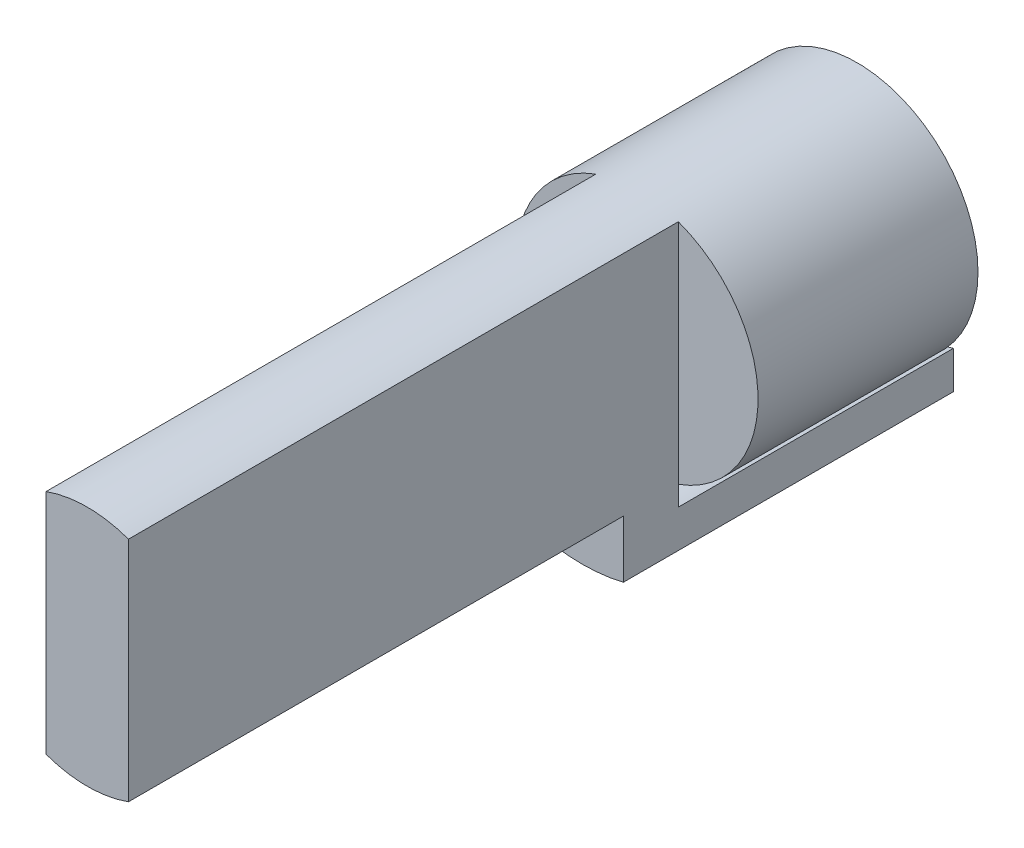
SolidWorks part; units mm, degrees
ref_plane "Front Plane" through (0, 0, 0) normal (0, 0, 1) x (1, 0, 0)
ref_plane "Top Plane" through (0, 0, 0) normal (0, 1, 0) x (1, 0, 0)
ref_plane "Right Plane" through (0, 0, 0) normal (1, 0, 0) x (0, 0, -1)
sketch "Sketch2" plane through (0, 0, 0) normal (0, 0, 1) x (1, 0, 0)
  circle A0 centre (0, 0) radius 11
  dimension "D1" = 22
extrude "Boss-Extrude1" add sketch "Sketch2" along normal blind 20
sketch "Sketch3" plane through (0, 0, 20) normal (0, 0, 1) x (1, 0, 0)
  line L2 (3.75, 10.3411) -> (3.75, -10.3411)
  line L4 (-3.75, 10.3411) -> (-3.75, -10.3411)
  line L5 (3.3225, 10.4862) -> (-3.3225, -10.4862) construction
  line L6 (3.3225, -10.4862) -> (-3.3225, 10.4862) construction
  circle A0 centre (0, 0) radius 11 construction
  arc A1 (-3.75, -10.3411) -> (3.75, -10.3411) centre (0, 0) ccw
  arc A2 (3.75, 10.3411) -> (-3.75, 10.3411) centre (0, 0) ccw
  point P0 (0, 0)
extrude "Boss-Extrude2" add sketch "Sketch3" along normal blind 50
sketch "Sketch4" plane through (0, 0, 70) normal (0, 0, 1) x (1, 0, 0)
  line L0 (-3.75, -10.3411) -> (-3.75, -12.1599)
  line L1 (3.75, -10.3411) -> (3.75, -12.1599)
  arc A0 (-3.75, -12.1599) -> (3.75, -12.1599) centre (0, 0) ccw
  arc A2 (-3.75, -10.3411) -> (3.75, -10.3411) centre (0, 0) ccw
  dimension "D1" = 25.45
extrude "Boss-Extrude3" add sketch "Sketch4" along normal blind 5 from surface starting at face at (-7.375, 0, 20)
sketch "Sketch5" plane through (0, 0, 70) normal (0, 0, 1) x (1, 0, 0)
  circle A0 centre (0, 0) radius 12.7
  circle A1 centre (0, 0) radius 16.4407
  dimension "D1" = 25.4
extrude "Cut-Extrude2" cut sketch "Sketch5" against normal through all both
sketch "Sketch6" plane through (0, 0, 20) normal (0, 0, -1) x (-1, 0, 0)
  line L0 (-3.75, -12.1337) -> (-3.75, -15.5543)
  line L1 (3.75, -12.1337) -> (3.75, -15.5543)
  arc A0 (-3.75, -15.5543) -> (3.75, -15.5543) centre (0, 0) ccw
  arc A1 (-3.75, -10.3411) -> (3.75, -10.3411) centre (0, 0) ccw construction
  arc A2 (-3.75, -12.1337) -> (3.75, -12.1337) centre (0, 0) ccw
  dimension "D1" = 5
extrude "Boss-Extrude4" add sketch "Sketch6" along normal blind 30 from surface starting at face at (0, -11.5437, 25)
sketch "Sketch7" plane through (0, 0, 0) normal (0, 0, -1) x (-1, 0, 0)
  line L0 (0, 0) -> (0, -28.7094) construction
  line L1 (3.75, -12.1337) -> (0, -12.1337)
  line L2 (3.75, -12.1337) -> (3.75, -28.7094)
  line L3 (0, -12.1337) -> (0, -28.7094)
  line L4 (3.75, -28.7094) -> (0, -28.7094)
extrude "Cut-Extrude3" cut sketch "Sketch7" against normal up to surface (25 mm away) from surface up to face at (0, -11.5437, 20) starting at face at (0, -14.097, -5)
